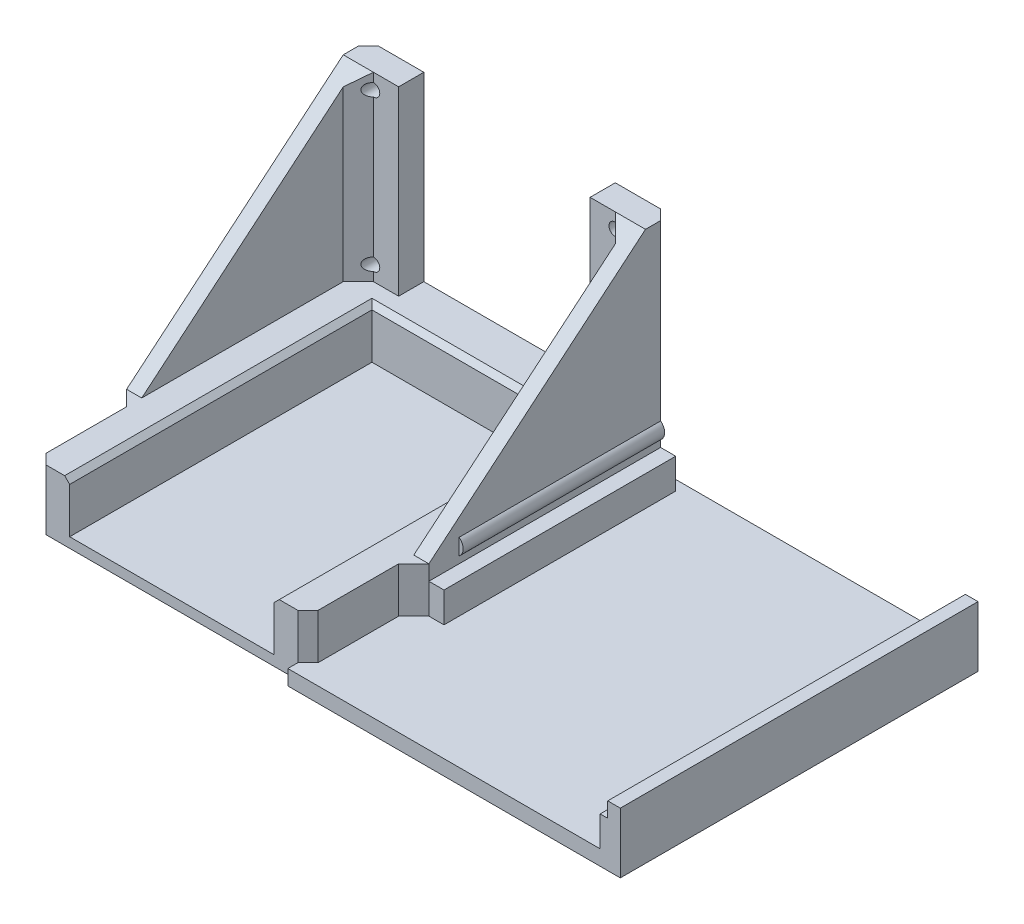
SolidWorks part; units mm, degrees
material "ABS"
ref_plane "Front Plane" through (0, 0, 0) normal (0, 0, 1) x (1, 0, 0)
ref_plane "Top Plane" through (0, 0, 0) normal (0, 1, 0) x (1, 0, 0)
ref_plane "Right Plane" through (0, 0, 0) normal (1, 0, 0) x (0, 0, -1)
sketch "Sketch1" plane through (0, 0, 0) normal (0, 0, 1) x (1, 0, 0)
  line L0 (-3, -3) -> (-3, 33)
  line L1 (0, 0) -> (5, 0) construction
  line L2 (0, 0) -> (0, 30) construction
  line L3 (0, 30) -> (5, 30) construction
  line L4 (48, 0) -> (48, 30) construction
  line L5 (-3, 33) -> (5, 33)
  line L6 (51, -3) -> (51, 33)
  line L7 (-3, -3) -> (5, -3)
  line L8 (43, 33) -> (51, 33)
  line L9 (-3, 33) -> (5, 33)
  line L10 (-3, 33) -> (-3, -3)
  line L11 (-3, -3) -> (5, -3)
  line L12 (5, 33) -> (5, -3)
  line L13 (51, 33) -> (43, 33)
  line L14 (51, 33) -> (51, -3)
  line L15 (51, -3) -> (43, -3)
  line L16 (43, 33) -> (43, -3)
  line L17 (-3, 33) -> (51, 33) construction
  line L18 (43, 30) -> (48, 30) construction
  line L19 (0, 30) -> (48, 30) construction
  line L20 (43, 0) -> (48, 0) construction
  line L21 (0, 0) -> (48, 0) construction
  line L22 (43, -3) -> (51, -3)
  line L23 (-3, -3) -> (51, -3) construction
  circle A0 centre (0, 30) radius 1.25
  circle A1 centre (48, 30) radius 1.25
  circle A2 centre (48, 0) radius 1.25
  circle A3 centre (0, 0) radius 1.25
  dimension "D3" = 2.5
  dimension "D1" = 30
  dimension "D2" = 48
  dimension "D7" = 8
  dimension "D8" = 8
  dimension "D6" = 3
  dimension "D4" = 2
  dimension "D5" = 2
extrude "Boss-Extrude1" add sketch "Sketch1" along normal blind 5 contours L12 L5 L0 L7 A3 A0 | L8 L16 L15 L6 A2 A1 region at (1.0353, 15, 0) region at (46.9647, 15, 0)
sketch "Sketch2" plane through (0, -3, 0) normal (0, -1, 0) x (1, 0, 0)
  line L1 (-3, 5) -> (51, 5)
  line L2 (-3, 5) -> (-3, 0)
  line L3 (-3, 0) -> (51, 0)
  line L4 (51, 5) -> (51, 0)
extrude "Boss-Extrude2" add sketch "Sketch2" along normal blind 12
sketch "Sketch4" plane through (0, 0, 5) normal (0, 0, 1) x (1, 0, 0)
  line L0 (51, -15) -> (-3, -15) construction
  line L1 (-3, -3) -> (51, -3)
  line L2 (-3, -3) -> (-3, -15)
  line L3 (-3, -15) -> (51, -15)
  line L4 (51, -3) -> (51, -15)
  line L6 (-3, -15) -> (-3, 33) construction
  line L7 (51, -15) -> (51, 33) construction
extrude "Boss-Extrude3" add sketch "Sketch4" along normal blind 64
sketch "Sketch5" plane through (0, -3, 0) normal (0, 1, 0) x (1, 0, 0)
  line L1 (3.7, -9) -> (44.3, -9)
  line L2 (3.7, -9) -> (3.7, -69.5)
  line L3 (3.7, -69.5) -> (44.3, -69.5)
  line L4 (44.3, -9) -> (44.3, -69.5)
  line L6 (24, -69) -> (24, -69.5) construction
  line L7 (51, -69) -> (-3, -69) construction
  line L8 (5, -5) -> (-3, -5) construction
  dimension "D1" = 40.6
  dimension "D2" = 60.5
  dimension "D3" = 4
extrude "Cut-Extrude1" cut sketch "Sketch5" against normal blind 10
sketch "Sketch7" plane through (-3, 0, 0) normal (-1, 0, 0) x (0, 0, 1)
  line L0 (0, 33) -> (0, -15)
  line L1 (0, -15) -> (0, 33) construction
  line L2 (0, -15) -> (48, -15)
  line L3 (69, -15) -> (0, -15) construction
  line L4 (48, -15) -> (48, -3)
  line L5 (69, -3) -> (5, -3) construction
  line L6 (48, -3) -> (5, 33)
  line L7 (5, 33) -> (0, 33)
extrude "Boss-Extrude4" add sketch "Sketch7" along normal blind 3
extrude "Boss-Extrude5" add sketch "Sketch7<2>" against normal blind 3 from surface starting at face at (51, 5, 24.6667)
sketch "Sketch7<2>" plane through (-3, 0, 0) normal (-1, 0, 0) x (0, 0, 1) same geometry as "Sketch7"
chamfer "Chamfer1" distance 2 angle 45 4 edges at (51, -9, 69) (-3, -9, 69) (54, 9, 0) (-6, 9, 0)
chamfer "Chamfer2" distance 1 angle 45 3 edges at (3.7, -3, 39) (24, -3, 9) (44.3, -3, 39)
chamfer "Chamfer3" distance 3 angle 45 4 edges at (51, -9, 48) (-3, -9, 48) (-3, 15, 5) (51, 15, 5)
sketch "Sketch8" plane through (0, -15, 0) normal (0, -1, 0) x (1, 0, 0)
  line L1 (115, 0) -> (49, 0)
  line L2 (115, 0) -> (115, 71)
  line L3 (115, 71) -> (49, 71)
  line L4 (49, 0) -> (49, 71)
  point P4 (1.25, 0)
  point P6 (1.25, 0)
  dimension "D1" = 66
  dimension "D2" = 71
extrude "Boss-Extrude6" add sketch "Sketch8" against normal blind 3
sketch "Sketch9" plane through (0, -12, 0) normal (0, 1, 0) x (1, 0, 0)
  line L0 (115, -71) -> (49, -71) construction
  line L1 (57, -2) -> (54, -2)
  line L2 (57, -2) -> (57, -48)
  line L3 (57, -48) -> (54, -48)
  line L4 (54, -2) -> (54, -48)
  line L5 (111, 0) -> (115, 0)
  line L6 (111, 0) -> (111, -71)
  line L7 (111, -71) -> (115, -71)
  line L8 (115, 0) -> (115, -71)
  line L9 (54, -2) -> (54, -48) construction
  line L10 (115, 0) -> (115, -71) construction
  dimension "D1" = 3
  dimension "D2" = 4
extrude "Boss-Extrude7" add sketch "Sketch9" along normal blind 6
sketch "Sketch11" plane through (0, 0, 2) normal (0, 0, -1) x (-1, 0, 0)
  line L10 (-54, -1.45) -> (-54, -4.65)
  arc A1 (-54, -4.65) -> (-54, -1.45) centre (-52.8, -3.05) cw
extrude "Boss-Extrude8" add sketch "Sketch11" against normal blind 40
sketch "Sketch12" plane through (0, -6, 0) normal (0, 1, 0) x (1, 0, 0)
  line L0 (111, -71) -> (115, -71) construction
  line L1 (112.5, 0) -> (115, 0)
  line L2 (112.5, 0) -> (112.5, -71)
  line L3 (112.5, -71) -> (115, -71)
  line L4 (115, 0) -> (115, -71)
  line L5 (115, -71) -> (115, 0) construction
  dimension "D1" = 2.5
extrude "Boss-Extrude9" add sketch "Sketch12" along normal blind 3
